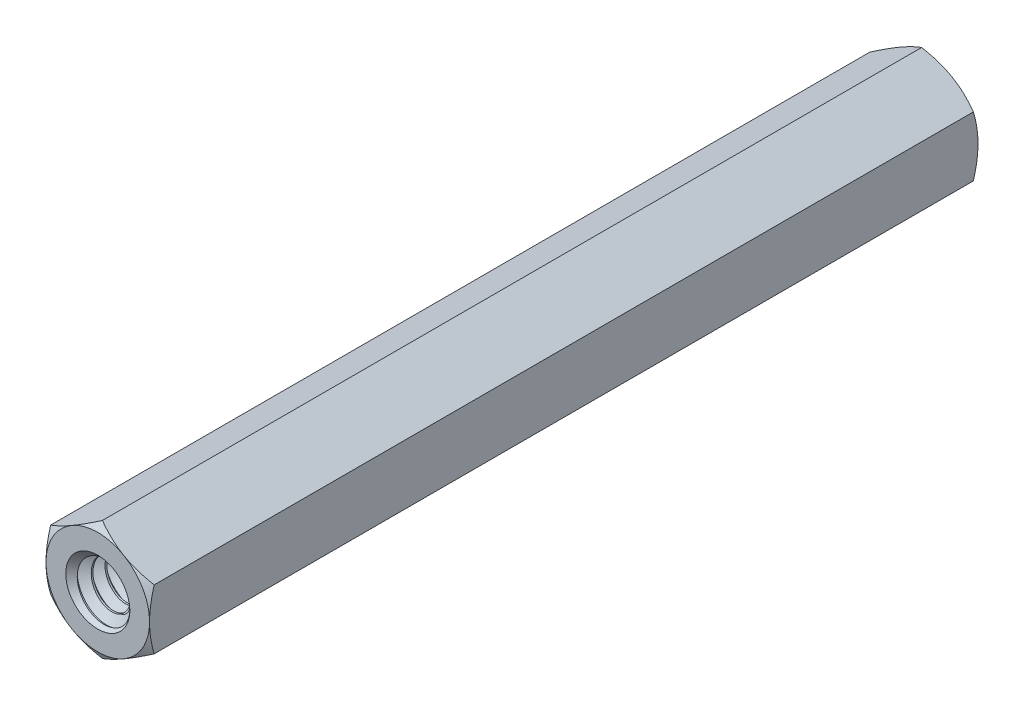
SolidWorks part; units mm, degrees
ref_plane "Front Plane" through (0, 0, 0) normal (0, 0, 1) x (1, 0, 0)
ref_plane "Top Plane" through (0, 0, 0) normal (0, 1, 0) x (1, 0, 0)
ref_plane "Right Plane" through (0, 0, 0) normal (1, 0, 0) x (0, 0, -1)
sketch "Sketch3" plane through (0, 0, 0) normal (1, 0, 0) x (0, 0, -1)
  line L0 (-19.05, 0) -> (19.05, 0) construction
  line L1 (0, 2.3813) -> (0, -2.3813) construction
  line L2 (-19.05, 1.4224) -> (-19.05, -1.4224) construction
  point P2 (12.7, 0)
  point P3 (-12.7, 0)
  dimension "D1" = 6.35
  dimension "Length" = 38.1
  dimension "Min Thread Length" = 6.35
  dimension "Thread Dia" = 2.8448
  dimension "Hex" = 4.7625
sketch "Sketch1" plane through (0, 0, 0) normal (0, 0, 1) x (1, 0, 0)
  line L1 (0, 2.7496) -> (-2.3813, 1.3748)
  line L2 (-2.3813, 1.3748) -> (-2.3813, -1.3748)
  line L3 (-2.3813, -1.3748) -> (0, -2.7496)
  line L4 (0, -2.7496) -> (2.3812, -1.3748)
  line L5 (2.3812, -1.3748) -> (2.3812, 1.3748)
  line L6 (2.3812, 1.3748) -> (0, 2.7496)
  circle A0 centre (0, 0) radius 2.3813 construction
  circle A1 centre (0, 0) radius 1.4224
extrude "Extrude1" add sketch "Sketch1" along normal up to vertex (19.05 mm away) and the other way up to vertex (19.05 mm away) up to point (0, 0, 19.05) other way up to point (0, 0, -19.05)
sketch "Sketch11" plane through (0, 0, -19.05) normal (0, 0, -1) x (-1, 0, 0)
  circle A0 centre (0, 0) radius 1.4224 construction
  circle A1 centre (0, 0) radius 1.4224
curve "Helix/Spiral1" pitch 0.635 height 38.735 radius 1.4224 centre (0, 0, -19.05) axis (0, 0, 1) start towards (0, 1, 0) parameters "Pitch"=0.635
sketch "Sketch12" plane through (0, 0, 0) normal (1, 0, 0) x (0, 0, -1)
  line L0 (19.6056, 1.4224) -> (19.05, 1.4224)
  line L1 (19.6056, 1.4224) -> (19.3675, 1.01)
  line L2 (19.3675, 1.01) -> (19.2881, 1.01)
  line L3 (19.2881, 1.01) -> (19.05, 1.4224)
  line L4 (19.3278, 1.01) -> (19.3278, 1.4224) construction
  line L5 (19.4866, 1.2162) -> (19.1691, 1.2162) construction
  dimension "D1" = 0.0794
  dimension "D2" = 0.3175
  dimension "D3" = 60
sweep "Sweep1" add profiles "Sketch12" path "Helix/Spiral1"
sketch "Sketch6" plane through (0, 0, -19.05) normal (0, 0, -1) x (-1, 0, 0)
  line L6 (0, 2.7496) -> (-2.3812, 1.3748)
  line L7 (-2.3812, 1.3748) -> (-2.3812, -1.3748)
  line L8 (-2.3812, -1.3748) -> (0, -2.7496)
  line L9 (0, -2.7496) -> (2.3813, -1.3748)
  line L10 (2.3813, -1.3748) -> (2.3813, 1.3748)
  line L11 (2.3813, 1.3748) -> (0, 2.7496)
  line L12 (0, 2.7496) -> (-2.3812, 1.3748)
  line L13 (-2.3812, 1.3748) -> (-2.3812, -1.3748)
  line L14 (-2.3812, -1.3748) -> (0, -2.7496)
  line L15 (0, -2.7496) -> (2.3813, -1.3748)
  line L16 (2.3813, -1.3748) -> (2.3813, 1.3748)
  line L17 (2.3813, 1.3748) -> (0, 2.7496)
  dimension "D1" = 0
extrude "Extrude2" cut sketch "Sketch6" along normal through all
sketch "Sketch7" plane through (0, 0, -19.05) normal (0, 0, -1) x (-1, 0, 0)
  circle A2 centre (0, 0) radius 1.4732
  circle A3 centre (0, 0) radius 1.4732
  dimension "D1" = 0.0508
extrude "Extrude3" cut sketch "Sketch7" against normal through all draft 43
sketch "Sketch8" plane through (0, 0, -19.05) normal (0, 0, -1) x (-1, 0, 0)
  circle A0 centre (0, 0) radius 2.3813 construction
  circle A1 centre (0, 0) radius 2.3813
extrude "Extrude4" cut sketch "Sketch8" against normal through all draft 60 flip side to cut
mirror "Mirror1" about plane through (0, 0, 0) normal (0, 0, 1) of "Extrude2", "Extrude3", "Extrude4"
sketch "Sketch9" plane through (0, 0, 0) normal (1, 0, 0) x (0, 0, -1)
  line L1 (-12.7, 1.4732) -> (12.7, 1.4732)
  line L2 (-12.7, 1.4732) -> (-12.7, 0)
  line L3 (-12.7, 0) -> (12.7, 0)
  line L4 (12.7, 1.4732) -> (12.7, 0)
  line L7 (-19.05, 0) -> (19.05, 0) construction
revolve "Revolve" add sketch "Sketch9" angle 360 about L0
sketch "Sketch10" plane through (0, 0, 0) normal (1, 0, 0) x (0, 0, -1)
  line L0 (19.05, 1.4224) -> (12.7, 1.4224)
  line L1 (-19.05, 1.4224) -> (-12.7, 1.4224)
  line L2 (12.7, 1.4224) -> (12.7, -1.4224)
  line L3 (-19.05, -1.4732) -> (-12.7, -1.4732)
  line L4 (-12.7, 1.4224) -> (-12.7, -1.4732)
  line L5 (12.7, -1.4224) -> (19.05, -1.4224)
equation "\"D1@Sketch3\" = \"Min Thread Length@Sketch3\""
equation "\"D3@Helix/Spiral1\" = \"Length@Sketch3\"+\"Pitch@Helix/Spiral1\""
equation "\"D1@Sketch12\" = \"Pitch@Helix/Spiral1\"*.125"
equation "\"D2@Sketch12\" = \"Pitch@Helix/Spiral1\"*.5"
